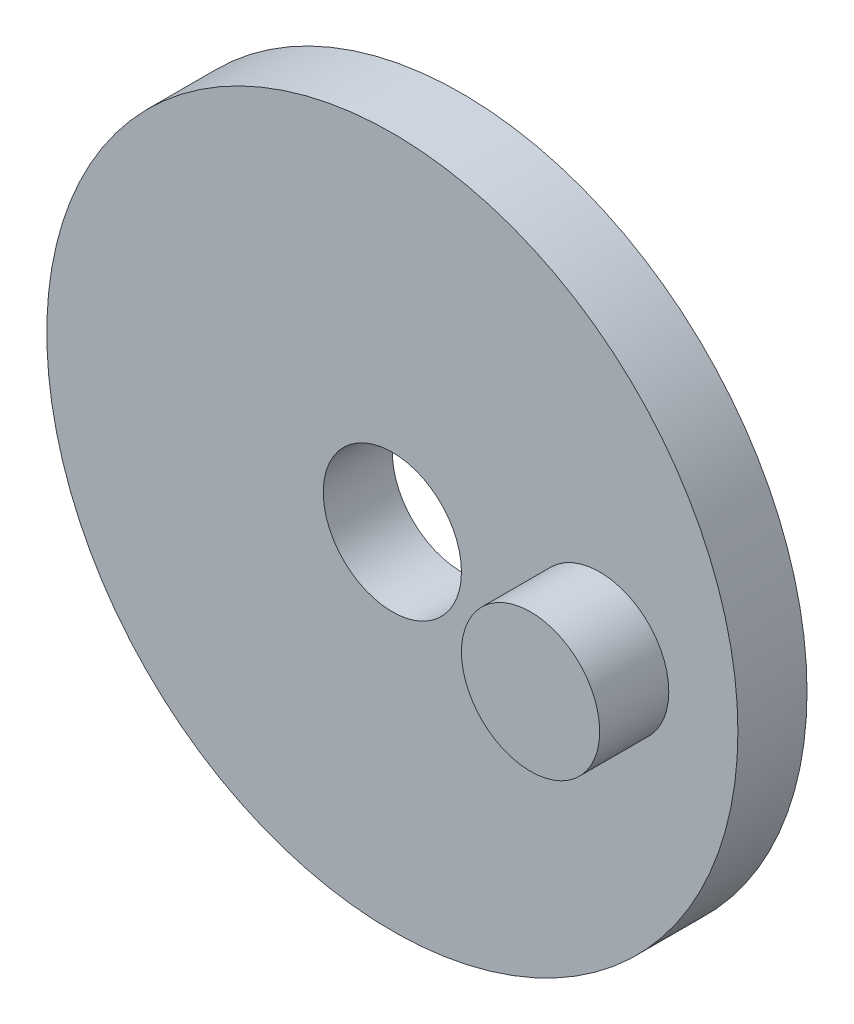
SolidWorks part; units mm, degrees
ref_plane "Front Plane" through (0, 0, 0) normal (0, 0, 1) x (1, 0, 0)
ref_plane "Top Plane" through (0, 0, 0) normal (0, 1, 0) x (1, 0, 0)
ref_plane "Right Plane" through (0, 0, 0) normal (1, 0, 0) x (0, 0, -1)
sketch "Sketch1" plane through (0, 0, 0) normal (0, 0, 1) x (1, 0, 0)
  circle A0 centre (0, 0) radius 50
  circle A1 centre (30, 0) radius 10
  circle A2 centre (0, 0) radius 10
  dimension "D1" = 100
extrude "Boss-Extrude1" add sketch "Sketch1" along normal blind 10
extrude "Boss-Extrude2" add sketch "Sketch1<2>" along normal blind 20 contours A1 region at (30, 0, 0)
sketch "Sketch1<2>" plane through (0, 0, 0) normal (0, 0, 1) x (1, 0, 0) same geometry as "Sketch1"
